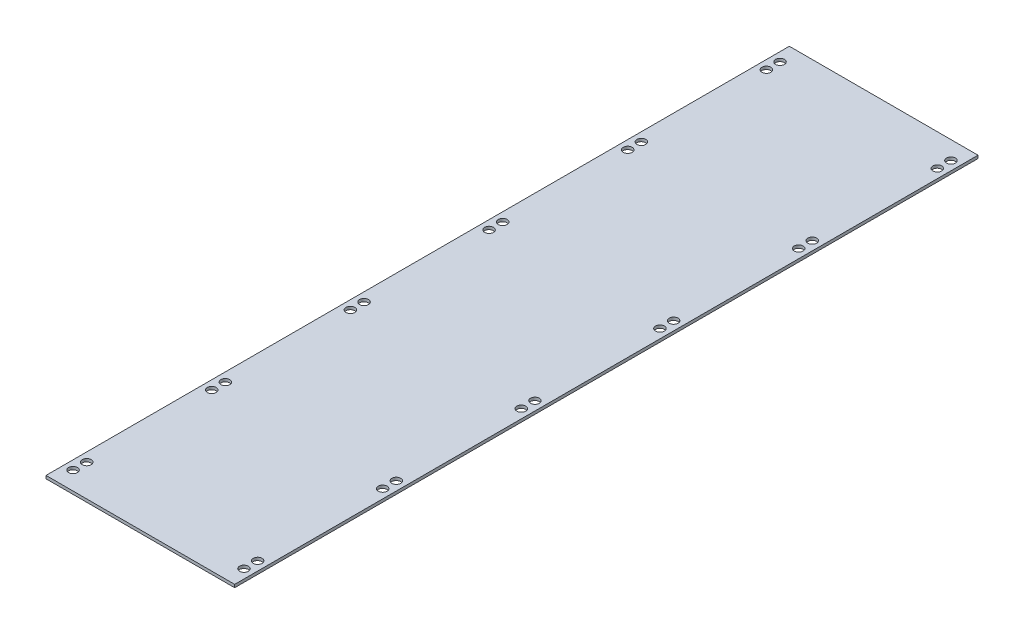
SolidWorks part; units mm, degrees
ref_plane "Front Plane" through (0, 0, 0) normal (0, 0, 1) x (1, 0, 0)
ref_plane "Top Plane" through (0, 0, 0) normal (0, 1, 0) x (1, 0, 0)
ref_plane "Right Plane" through (0, 0, 0) normal (1, 0, 0) x (0, 0, -1)
sketch "Sketch1" plane through (0, 0, 0) normal (0, 1, 0) x (1, 0, 0)
  line L1 (0, 0) -> (83, 0)
  line L2 (0, 0) -> (0, 327)
  line L3 (0, 327) -> (83, 327)
  line L4 (83, 0) -> (83, 327)
  dimension "D1" = 83
  dimension "D2" = 327
extrude "Boss-Extrude1" add sketch "Sketch1" along normal blind 1.3
sketch "Sketch2" plane through (0, 1.3, 0) normal (0, 1, 0) x (1, 0, 0)
  line L0 (0, 327) -> (0, 0) construction
  line L1 (83, 327) -> (0, 327) construction
  circle A0 centre (3.9, 319) radius 1.95
  circle A1 centre (3.9, 313) radius 1.95
  circle A2 centre (79.1, 319) radius 1.95
  circle A3 centre (79.1, 313) radius 1.95
  circle A4 centre (79.1, 258) radius 1.95
  circle A5 centre (79.1, 252) radius 1.95
  circle A6 centre (79.1, 197) radius 1.95
  circle A7 centre (79.1, 191) radius 1.95
  circle A8 centre (79.1, 136) radius 1.95
  circle A9 centre (79.1, 130) radius 1.95
  circle A10 centre (79.1, 75) radius 1.95
  circle A11 centre (79.1, 69) radius 1.95
  circle A12 centre (79.1, 14) radius 1.95
  circle A13 centre (79.1, 8) radius 1.95
  circle A14 centre (3.9, 258) radius 1.95
  circle A15 centre (3.9, 252) radius 1.95
  circle A16 centre (3.9, 197) radius 1.95
  circle A17 centre (3.9, 191) radius 1.95
  circle A18 centre (3.9, 136) radius 1.95
  circle A19 centre (3.9, 130) radius 1.95
  circle A20 centre (3.9, 75) radius 1.95
  circle A21 centre (3.9, 69) radius 1.95
  circle A22 centre (3.9, 14) radius 1.95
  circle A23 centre (3.9, 8) radius 1.95
  dimension "D1" = 3.9
  dimension "D2" = 3.9
  dimension "D3" = 3.9
  dimension "D4" = 3.9
  dimension "D5" = 6
  dimension "D6" = 8
  dimension "D7" = 2
  dimension "D8" = 6
extrude "Cut-Extrude1" cut sketch "Sketch2" against normal blind 10
